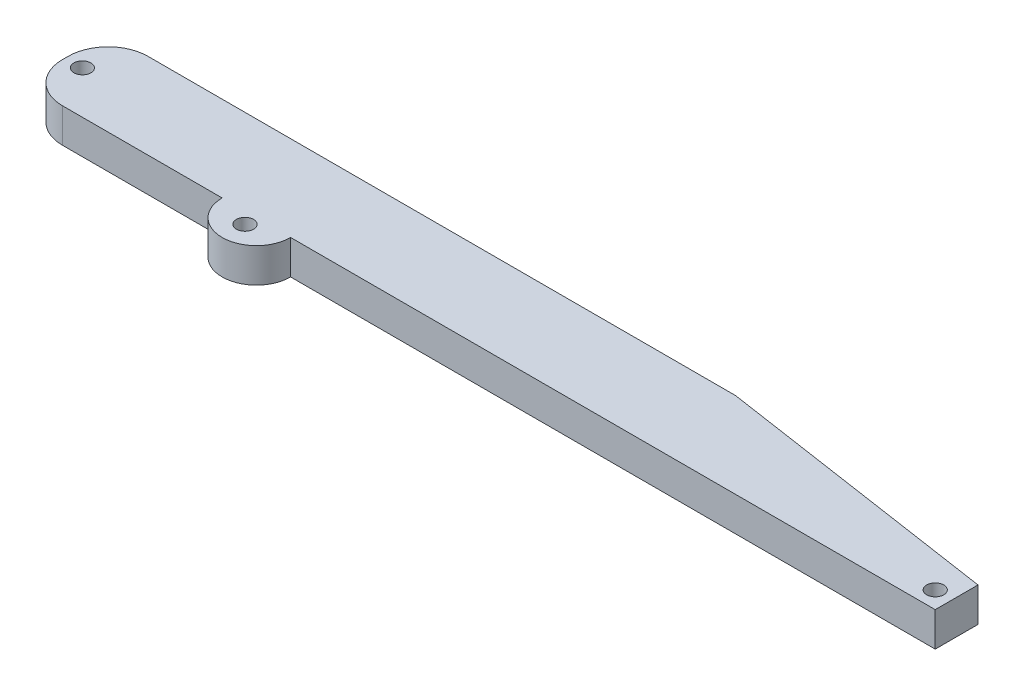
SolidWorks part; units mm, degrees
ref_plane "Front Plane" through (0, 0, 0) normal (0, 0, 1) x (1, 0, 0)
ref_plane "Top Plane" through (0, 0, 0) normal (0, 1, 0) x (1, 0, 0)
ref_plane "Right Plane" through (0, 0, 0) normal (1, 0, 0) x (0, 0, -1)
sketch "Sketch2" plane through (0, 0, 0) normal (0, 1, 0) x (1, 0, 0)
  line L11 (-80, 7.5) -> (80, 7.5)
  line L12 (-80, 7.5) -> (-80, -7.5)
  line L13 (-80, -7.5) -> (80, -7.5)
  line L14 (80, 7.5) -> (80, -7.5)
  dimension "D2" = 80
  dimension "D1" = 160
  dimension "D3" = 15
  dimension "D4" = 7.5
extrude "Boss-Extrude1" add sketch "Sketch2" along normal blind 6
sketch "Sketch4" plane through (0, 0, 0) normal (0, 1, 0) x (1, 0, 0)
  line L0 (-80, -7.5) -> (80, -7.5) construction
  line L1 (-45, -7.5) -> (-33, -7.5)
  arc A0 (-45, -7.5) -> (-33, -7.5) centre (-39, -7.5) ccw
  dimension "D1" = 6
  dimension "D2" = 35
  dimension "D3" = 12
extrude "Boss-Extrude2" add sketch "Sketch4" along normal blind 6
sketch "Sketch5" plane through (0, 6, 0) normal (0, 1, 0) x (1, 0, 0)
  line L0 (-80, -7.5) -> (-45, -7.5) construction
  line L1 (-80, 7.5) -> (-80, -7.5) construction
  line L2 (80, -7.5) -> (80, 7.5) construction
  line L3 (-33, -7.5) -> (80, -7.5) construction
  circle A0 centre (-77, 0) radius 1.5
  circle A1 centre (-39, -9.5) radius 1.5
  circle A2 centre (77, -4.5) radius 1.5
  arc A3 (-45, -7.5) -> (-33, -7.5) centre (-39, -7.5) ccw construction
  point P10 (-39, -13.5)
  point P19 (71.1136, 12.7339)
  dimension "D1" = 3
  dimension "D2" = 3
  dimension "D3" = 3
  dimension "D4" = 6
  dimension "D5" = 4
  dimension "D6" = 7.5
  dimension "D7" = 3
  dimension "D8" = 3
  dimension "D9" = 3
extrude "Cut-Extrude1" cut sketch "Sketch5" against normal through all
sketch "Sketch6" plane through (0, 6, 0) normal (0, 1, 0) x (1, 0, 0)
  line L0 (80, 0) -> (80, 7.5)
  line L1 (80, -7.5) -> (80, 7.5) construction
  line L2 (80, 7.5) -> (30, 7.5)
  line L3 (80, 7.5) -> (-80, 7.5) construction
  line L4 (30, 7.5) -> (80, 0)
  dimension "D1" = 50
extrude "Cut-Extrude2" cut sketch "Sketch6" against normal through all
fillet "Fillet1" radius 7 2 edges at (-80, 3, -7.5) (-80, 3, 7.5)
